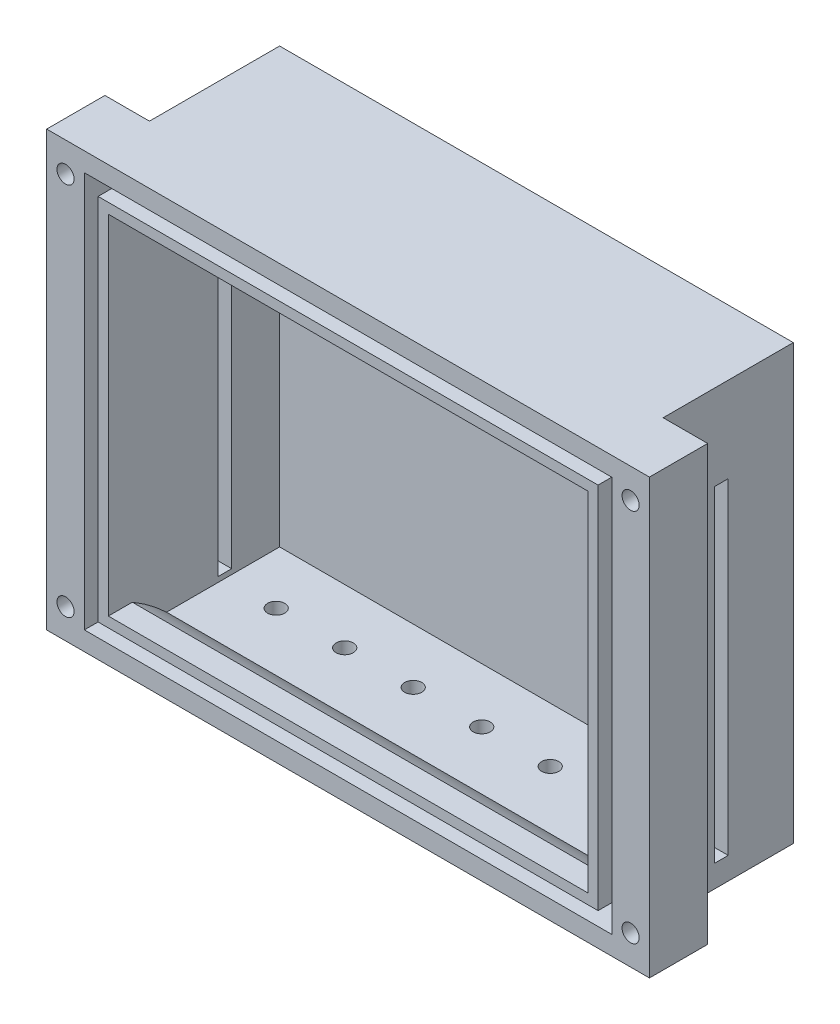
SolidWorks part; units mm, degrees
material "ABS"
ref_plane "Front Plane" through (0, 0, 0) normal (0, 0, 1) x (1, 0, 0)
ref_plane "Top Plane" through (0, 0, 0) normal (0, 1, 0) x (1, 0, 0)
ref_plane "Right Plane" through (0, 0, 0) normal (1, 0, 0) x (0, 0, -1)
sketch "Sketch1" plane through (0, 0, 0) normal (0, 1, 0) x (1, 0, 0)
  circle A0 centre (0, 0) radius 172.5
  dimension "D1" = 345
extrude "Boss-Extrude1" add sketch "Sketch1" along normal blind 10
sketch "Sketch2" plane through (0, 10, 0) normal (0, 1, 0) x (1, 0, 0)
  circle A0 centre (-75.91, -178.72) radius 48.41
  circle A1 centre (75.91, -178.72) radius 48.41
  dimension "D1" = 96.82
  dimension "D2" = 96.82
  dimension "D3" = 151.82
  dimension "D4" = 0
  dimension "D5" = 178.72
  dimension "D6" = 75.91
extrude "Cut-Extrude1" cut sketch "Sketch2" against normal blind 10
sketch "Sketch3" plane through (0, 10, 0) normal (0, 1, 0) x (1, 0, 0)
  line L0 (-75.91, -178.72) -> (75.91, -178.72)
  line L1 (-98.9683, -119.81) -> (98.9683, -119.81)
  line L2 (0, -178.72) -> (0, -205.4095)
  line L3 (0, -116.81) -> (0, -103.1109)
  line L4 (-97.8835, -116.81) -> (97.8835, -116.81)
  arc A0 (97.8835, -116.81) -> (-97.8835, -116.81) centre (0, 0) ccw
  arc A1 (98.9683, -119.81) -> (-98.9683, -119.81) centre (0, 0) ccw
  dimension "D1" = 304.8
  dimension "D2" = 3
  dimension "D4" = 0
extrude "Boss-Extrude2" add sketch "Sketch3" along normal blind 5 contours L1 A1 A0 L4 region at (0, 10, -154.9849)
sketch "Sketch4" plane through (0, 10, 0) normal (0, 1, 0) x (1, 0, 0)
  line L0 (-28.2612, -170.1692) -> (28.2612, -170.1692)
  line L1 (28.2612, -170.1692) -> (28.2612, -183.8361)
  line L2 (28.2612, -183.8361) -> (-30.3005, -183.8361)
  line L3 (-30.3005, -183.8361) -> (-28.2612, -170.1692)
extrude "Cut-Extrude2" cut sketch "Sketch4" against normal blind 497
sketch "Sketch5" plane through (0, 10, 0) normal (0, 1, 0) x (1, 0, 0)
  line L0 (-166.525, 159.566) -> (-166.525, -120.1627)
  line L1 (166.525, 178.4393) -> (166.525, -124.881)
  line L2 (-148.2899, 170.4208) -> (120.6541, 170.4208)
  line L3 (28.2612, -170.1692) -> (-28.2612, -170.1692) construction
  line L5 (-166.525, 170.4208) -> (166.525, 170.4208)
  line L6 (-166.525, 170.4208) -> (-166.525, -186.2191)
  line L7 (-166.525, -186.2191) -> (166.525, -186.2191)
  line L8 (166.525, 170.4208) -> (166.525, -186.2191)
  line L9 (-215.4787, 226.3504) -> (214.5081, 226.3504)
  line L10 (-215.4787, 226.3504) -> (-215.4787, -259.9327)
  line L11 (-215.4787, -259.9327) -> (214.5081, -259.9327)
  line L12 (214.5081, 226.3504) -> (214.5081, -259.9327)
  arc M6 (102.8405, -138.4922) -> (-102.8405, -138.4922) centre (0, 0) ccw
  dimension "D1" = 333.05
  dimension "D2" = 166.525
  dimension "D3" = 340.59
extrude "Cut-Extrude6" cut sketch "Sketch5" against normal blind 497 contours L2 M6 | L1 M6 | L0 M6 region at (-168.9186, 10, 0) region at (0, 10, -171.2529) region at (168.9186, 10, 0)
sketch "Sketch6" plane through (0, 10, 0) normal (0, 1, 0) x (1, 0, 0)
  line L0 (-97.8835, -116.81) -> (97.8835, -116.81)
  line L1 (-97.8835, -116.81) -> (-97.8835, -61.81)
  line L2 (97.8835, -116.81) -> (97.8835, -61.81)
  line L3 (97.8835, -61.81) -> (-97.8835, -61.81)
  line L4 (92.8835, -66.81) -> (-92.8835, -66.81)
  line L5 (-92.8835, -111.81) -> (-92.8835, -66.81)
  line L6 (-92.8835, -111.81) -> (92.8835, -111.81)
  line L7 (92.8835, -111.81) -> (92.8835, -66.81)
  dimension "D1" = 55
  dimension "D2" = 5
extrude "Boss-Extrude3" add sketch "Sketch6" along normal blind 133.35
sketch "Sketch7" plane through (0, 10, 0) normal (0, 1, 0) x (1, 0, 0)
  line L1 (-92.8835, -66.81) -> (92.8835, -66.81)
  line L2 (-92.8835, -66.81) -> (-92.8835, -111.81)
  line L3 (-92.8835, -111.81) -> (92.8835, -111.81)
  line L4 (92.8835, -66.81) -> (92.8835, -111.81)
extrude "Boss-Extrude4" add sketch "Sketch7" along normal blind 5
sketch "Sketch8" plane through (0, 10, 0) normal (0, 1, 0) x (1, 0, 0)
  line L0 (-112.8835, -61.81) -> (-112.8835, -101.2671)
  line L1 (-97.8835, -61.81) -> (97.8835, -61.81)
  line L2 (-97.8835, -61.81) -> (-97.8835, -115.8298)
  line L4 (97.8835, -61.81) -> (97.8835, -115.8298)
  line L6 (112.8835, -46.81) -> (112.8835, -101.2671)
  line L7 (-88.0285, -46.81) -> (112.8835, -46.81)
  line L8 (-112.8835, -46.81) -> (-112.8835, -131.81) construction
  line L9 (-112.8835, -131.81) -> (112.8835, -131.81) construction
  line L10 (112.8835, -46.81) -> (112.8835, -131.81) construction
  line L11 (74.9923, -131.81) -> (76.4976, -131.81)
  line L12 (-97.8835, -116.81) -> (97.8835, -116.81) construction
  line L13 (97.8835, -61.81) -> (97.8835, -116.81) construction
  line L14 (-97.8835, -61.81) -> (-97.8835, -116.81) construction
  line L15 (-112.8835, -46.81) -> (112.8835, -46.81) construction
  line L18 (-112.8835, -61.81) -> (-88.0285, -61.81)
  line L19 (-88.0285, -46.81) -> (-88.0285, -61.81)
  arc A1 (-112.8835, -101.2671) -> (-96.7117, -116.81) centre (0, 0) ccw
  arc A5 (97.8835, -115.8298) -> (112.8835, -101.2671) centre (0, 0) ccw
  line M3 (-97.8835, -116.81) -> (-97.8835, -61.81)
  line M5 (97.8835, -61.81) -> (97.8835, -116.81)
  dimension "D1" = 15
extrude "Boss-Extrude5" add sketch "Sketch8" along normal blind 8 contours L0 A1 L18 M3 | A5 L6 L7 L19 L1 M5 region at (-104.9975, 10, 85.5341) region at (29.9995, 10, 60.2371)
chamfer "Chamfer1" distance 8 angle 38 3 edges at (-97.8835, 18, 88.8199) (4.9275, 18, 61.81) (97.8835, 18, 88.8199) first distance on face at (-97.8835, 51.1, 100.8157) first distance on face at (-50.228, 47.3375, 61.81) first distance on face at (97.8835, 51.1, 100.8157)
fillet "Fillet1" radius 38 3 edges at (-97.8835, 26, 88.8199) (4.9275, 26, 61.81) (97.8835, 26, 88.8199)
sketch "Sketch9" plane through (0, 10, 0) normal (0, 1, 0) x (1, 0, 0)
  circle A0 centre (0, 0) radius 374.0793
extrude "Cut-Extrude7" cut sketch "Sketch9" against normal blind 93
sketch "Sketch10" plane through (0, 10, 0) normal (0, -1, 0) x (1, 0, 0)
  circle A0 centre (0, 0) radius 152.4
  circle A1 centre (0, 0) radius 229.3861
extrude "Cut-Extrude8" cut sketch "Sketch10" against normal blind 93 and the other way blind 93
sketch "Sketch11" plane through (0, 143.35, 0) normal (0, 1, 0) x (1, 0, 0)
  line L0 (47.0835, -61.81) -> (47.0835, -116.81)
  line L1 (97.8835, -61.81) -> (-97.8835, -61.81) construction
  line L2 (-97.8835, -116.81) -> (97.8835, -116.81) construction
  line L3 (97.8835, -116.81) -> (97.8835, -61.81) construction
  line L4 (47.0835, -61.81) -> (-97.8835, -61.81)
  line L5 (-97.8835, -61.81) -> (-97.8835, -116.81)
  line L6 (-97.8835, -116.81) -> (47.0835, -116.81)
  line L8 (-140.8808, -21.3721) -> (150.5625, -21.3721)
  line L9 (-140.8808, -21.3721) -> (-140.8808, -156.1708)
  line L10 (-140.8808, -156.1708) -> (150.5625, -156.1708)
  line L11 (150.5625, -21.3721) -> (150.5625, -156.1708)
  dimension "D1" = 50.8
extrude "Cut-Extrude9" cut sketch "Sketch11" against normal blind 143
sketch "Sketch12" plane through (0, 143.35, 0) normal (0, 1, 0) x (1, 0, 0)
  line L1 (47.0835, -61.81) -> (52.0835, -61.81)
  line L2 (47.0835, -61.81) -> (47.0835, -116.81)
  line L3 (47.0835, -116.81) -> (52.0835, -116.81)
  line L4 (52.0835, -61.81) -> (52.0835, -116.81)
  dimension "D1" = 5
extrude "Boss-Extrude6" add sketch "Sketch12" against normal up to surface (133.35 mm away) up to face at (-25.4, 10, 89.31)
sketch "Sketch14" plane through (0, 143.35, 0) normal (0, 1, 0) x (1, 0, 0)
  line L1 (-92.8835, -66.81) -> (47.0835, -66.81)
  line L2 (-92.8835, -66.81) -> (-92.8835, -111.81)
  line L3 (-92.8835, -111.81) -> (47.0835, -111.81)
  line L4 (47.0835, -66.81) -> (47.0835, -111.81)
extrude "Boss-Extrude7" add sketch "Sketch14" against normal blind 5
sketch "Sketch15" plane through (0, 0, 116.81) normal (0, 0, 1) x (1, 0, 0)
  line L1 (-92.8835, 138.35) -> (47.0835, 138.35)
  line L2 (-92.8835, 138.35) -> (-92.8835, 15)
  line L3 (-92.8835, 15) -> (47.0835, 15)
  line L4 (47.0835, 138.35) -> (47.0835, 15)
extrude "Cut-Extrude11" cut sketch "Sketch15" against normal blind 13
sketch "Sketch16" plane through (0, 0, 116.81) normal (0, 0, 1) x (1, 0, 0)
  line L0 (-107.8835, 143.35) -> (-107.8835, 10)
  line L1 (-92.8835, 138.35) -> (47.0835, 138.35)
  line L2 (-92.8835, 138.35) -> (-92.8835, 15)
  line L3 (-92.8835, 15) -> (47.0835, 15)
  line L4 (47.0835, 138.35) -> (47.0835, 15)
  line L6 (62.0835, 143.35) -> (62.0835, 10)
  line L8 (-107.8835, 143.35) -> (62.0835, 143.35)
  line L9 (-107.8835, 10) -> (62.0835, 10)
  line L10 (-107.8835, 153.35) -> (-107.8835, 0) construction
  line L11 (-107.8835, 0) -> (62.0835, 0) construction
  line L12 (62.0835, 153.35) -> (62.0835, 0) construction
  line L13 (-107.8835, 153.35) -> (62.0835, 153.35) construction
  line L14 (-92.8835, 76.675) -> (47.0835, 76.675)
  line L15 (-92.8835, 127.475) -> (47.0835, 127.475)
  line L16 (-92.8835, 127.475) -> (-92.8835, 25.875)
  line L17 (-92.8835, 25.875) -> (47.0835, 25.875)
  line L18 (47.0835, 127.475) -> (47.0835, 25.875)
  line L19 (-22.9, 127.475) -> (-22.9, 25.875)
  point P22 (-92.8835, 76.675)
  point P25 (-22.9, 138.35)
  line M11 (47.0835, 15) -> (-92.8835, 15)
  line M12 (-92.8835, 15) -> (-92.8835, 138.35)
  line M13 (-92.8835, 138.35) -> (47.0835, 138.35)
  line M14 (47.0835, 138.35) -> (47.0835, 15)
  line M15 (-97.8835, 10) -> (52.0835, 10)
  line M16 (52.0835, 10) -> (52.0835, 143.35)
  line M17 (52.0835, 143.35) -> (-97.8835, 143.35)
  line M18 (-97.8835, 143.35) -> (-97.8835, 10)
  dimension "D2" = 101.6
  dimension "D3" = 0
  dimension "D4" = 0
  dimension "D5" = 0
  dimension "D1" = 15
extrude "Boss-Extrude9" add sketch "Sketch16" against normal blind 17 contours L0 L9 L8 M18 | L4 L2 M18 M15 M16 M17 M14 M11 M12 M13 | L9 L6 L8 M16 | L15 M12 M14 M13 | L17 M12 M11 M14 region at (-102.8835, 76.675, 116.81) region at (-22.9, 141.3432, 116.81) region at (57.0835, 76.675, 116.81) region at (-22.9, 132.9125, 116.81) region at (-22.9, 20.4375, 116.81)
sketch "Sketch17" plane through (0, 0, 116.81) normal (0, 0, 1) x (1, 0, 0)
  line L0 (-95.8835, 130.475) -> (-95.8835, 22.875)
  line L1 (-92.8835, 127.475) -> (47.0835, 127.475)
  line L2 (-92.8835, 127.475) -> (-92.8835, 25.875)
  line L3 (-92.8835, 25.875) -> (47.0835, 25.875)
  line L4 (47.0835, 127.475) -> (47.0835, 25.875)
  line L5 (-95.8835, 22.875) -> (50.0835, 22.875)
  line L6 (50.0835, 130.475) -> (50.0835, 22.875)
  line L7 (-95.8835, 130.475) -> (50.0835, 130.475)
  line L8 (-99.8835, 134.475) -> (54.0835, 134.475)
  line L9 (54.0835, 134.475) -> (54.0835, 18.875)
  line L10 (-99.8835, 18.875) -> (54.0835, 18.875)
  line L11 (-99.8835, 134.475) -> (-99.8835, 18.875)
  dimension "D1" = 3
  dimension "D2" = 4
extrude "Cut-Extrude12" cut sketch "Sketch17" against normal blind 10 contours L8 L11 L10 L9 L0 L7 L6 L5 region at (-22.9, 132.5497, 116.81)
sketch "Sketch20" plane through (0, 0, 116.81) normal (0, 0, 1) x (1, 0, 0)
  line L0 (-107.8835, 143.35) -> (-107.8835, 10) construction
  line L1 (-110.8835, 146.35) -> (65.0835, 146.35)
  line L2 (-110.8835, 146.35) -> (-110.8835, 7)
  line L3 (-110.8835, 7) -> (65.0835, 7)
  line L4 (65.0835, 146.35) -> (65.0835, 7)
  line L5 (62.0835, 143.35) -> (62.0835, 10) construction
  line L6 (-107.8835, 10) -> (62.0835, 10) construction
  line L7 (-107.8835, 143.35) -> (62.0835, 143.35) construction
  line L9 (-107.8835, 143.35) -> (62.0835, 143.35)
  line L10 (-107.8835, 143.35) -> (-107.8835, 10)
  line L11 (-107.8835, 10) -> (62.0835, 10)
  line L12 (62.0835, 143.35) -> (62.0835, 10)
  line L13 (-110.8835, 7) -> (65.0835, 7)
  line L14 (-110.8835, 7) -> (-110.8835, 13.35)
  line L15 (-110.8835, 13.35) -> (65.0835, 13.35)
  line L16 (65.0835, 7) -> (65.0835, 13.35)
  line M13 (-107.8835, 10) -> (62.0835, 10)
  line M14 (62.0835, 10) -> (62.0835, 143.35)
  dimension "D1" = 3
  dimension "D2" = 3
  dimension "D3" = 3
  dimension "D4" = 3
  dimension "D5" = 6.35
chamfer "Chamfer2" distance 10 angle 30 2 edges at (-22.9, 25.875, 99.81) (-22.9, 127.475, 99.81) first distance on face at (-22.9, 25.875, 108.31) first distance on face at (-22.9, 132.9125, 99.81)
extrude "Cut-Extrude17" cut sketch "Sketch20" against normal blind 177.5 contours L15 L2 L3 L4 L10 M14 M13 | L15 L10 M13 M14 region at (-22.9, 8.6165, 116.81) region at (-22.9, 11.675, 116.81)
sketch "Sketch25" plane through (0, 13.35, 0) normal (0, -1, 0) x (-1, 0, 0)
  line L1 (-47.0835, -66.81) -> (92.8835, -66.81)
  line L2 (-47.0835, -66.81) -> (-47.0835, -105.5835)
  line L3 (-47.0835, -105.5835) -> (92.8835, -105.5835)
  line L4 (92.8835, -66.81) -> (92.8835, -105.5835)
extrude "Boss-Extrude11" add sketch "Sketch25" against normal blind 5
sketch "Sketch26" plane through (0, 0, 116.81) normal (0, 0, 1) x (1, 0, 0)
  line L0 (-107.8835, 143.35) -> (-107.8835, 13.35) construction
  line L1 (-110.8835, 143.35) -> (-107.8835, 143.35)
  line L2 (-110.8835, 143.35) -> (-110.8835, 13.35)
  line L3 (-110.8835, 13.35) -> (-107.8835, 13.35)
  line L4 (65.0835, 143.35) -> (65.0835, 13.35)
  line L5 (62.0835, 143.35) -> (62.0835, 13.35) construction
  line L6 (62.0835, 13.35) -> (65.0835, 13.35)
  line L8 (-107.8835, 143.35) -> (-107.8835, 13.35)
  line L10 (62.0835, 143.35) -> (62.0835, 13.35)
  line L11 (62.0835, 143.35) -> (65.0835, 143.35)
  dimension "D1" = 3
  dimension "D2" = 3
extrude "Boss-Extrude12" add sketch "Sketch26" against normal up to surface (17 mm away) up to face at (57.0835, 78.35, 99.81)
sketch "Sketch18" plane through (0, 0, 116.81) normal (0, 0, 1) x (1, 0, 0)
  line L7 (-99.8835, 134.475) -> (-99.8835, 18.875) construction
  line L8 (54.0835, 134.475) -> (54.0835, 18.875) construction
  circle A2 centre (-105.3835, 22) radius 2.5
  circle A3 centre (59.5835, 22) radius 2.5
  circle A4 centre (59.5835, 131.35) radius 2.5
  circle A5 centre (-105.3835, 131.35) radius 2.5
  point P10 (-22.9, 76.675)
  dimension "D4" = 5
  dimension "D5" = 5
  dimension "D10" = 5.5
  dimension "D12" = 5.5
extrude "Cut-Extrude19" cut sketch "Sketch18" against normal blind 26
sketch "Sketch27" plane through (0, 0, 66.81) normal (0, 0, 1) x (1, 0, 0)
  line L0 (47.0835, 138.35) -> (-92.8835, 138.35) construction
  line L1 (-22.9165, 138.35) -> (37.0835, 138.35)
  line L2 (-22.9165, 138.35) -> (-22.9165, 135.35)
  line L3 (-22.9165, 135.35) -> (37.0835, 135.35)
  line L4 (37.0835, 138.35) -> (37.0835, 135.35)
  line L5 (47.0835, 18.35) -> (47.0835, 138.35) construction
  dimension "D1" = 60
  dimension "D2" = 0
  dimension "D3" = 70
  dimension "D4" = 3
extrude "Cut-Extrude20" cut sketch "Sketch27" against normal blind 23
sketch "Sketch28" plane through (0, 18.35, 0) normal (0, 1, 0) x (1, 0, 0)
  line L0 (-92.8835, -99.81) -> (-92.8835, -66.81) construction
  line L1 (-92.8835, -66.81) -> (47.0835, -66.81) construction
  circle A0 centre (-77.8835, -82.81) radius 2.5
  circle A1 centre (-57.8835, -82.81) radius 2.5
  circle A2 centre (-37.8835, -82.81) radius 2.5
  circle A3 centre (-17.8835, -82.81) radius 2.5
  circle A4 centre (2.1165, -82.81) radius 2.5
  circle A5 centre (22.1165, -82.81) radius 2.5
  dimension "D1" = 5
  dimension "D2" = 15
  dimension "D3" = 16
  dimension "D4" = 6
extrude "Cut-Extrude21" cut sketch "Sketch28" against normal blind 10
sketch "Sketch29" plane through (0, 0, 61.81) normal (0, 0, -1) x (-1, 0, 0)
  line L0 (97.8835, 13.35) -> (-52.0835, 13.35) construction
  line L1 (39.6909, 98.35) -> (54.6909, 98.35)
  line L2 (39.6909, 98.35) -> (39.6909, 68.35)
  line L3 (39.6909, 68.35) -> (54.6909, 68.35)
  line L4 (54.6909, 98.35) -> (54.6909, 68.35)
  dimension "D1" = 30
  dimension "D2" = 15
  dimension "D3" = 55
extrude "Boss-Extrude13" add sketch "Sketch29" along normal blind 10
sketch "Sketch30" plane through (-54.6909, 0, 0) normal (-1, 0, 0) x (0, 0, 1)
  line L0 (51.81, 68.35) -> (61.81, 68.35) construction
  line L1 (61.81, 98.35) -> (57.81, 98.35)
  line L2 (61.81, 98.35) -> (61.81, 68.35)
  line L3 (61.81, 68.35) -> (57.81, 68.35)
  line L4 (57.81, 98.35) -> (57.81, 68.35)
  line L5 (57.81, 94.85) -> (61.81, 94.85)
  line L6 (57.81, 71.85) -> (61.81, 71.85)
  point P11 (59.81, 98.35)
  dimension "D1" = 4
  dimension "D2" = 3.5
  dimension "D3" = 3.5
extrude "Cut-Extrude22" cut sketch "Sketch30" against normal blind 21 contours L4 L6 L2 L5 region at (-54.6909, 83.35, 59.81)
chamfer "Chamfer3" distance 6 angle 45 2 edges at (-47.1909, 68.35, 61.81) (-47.1909, 98.35, 61.81)
sketch "Sketch31" plane through (0, 0, 116.81) normal (0, 0, 1) x (1, 0, 0)
  line L0 (-110.8835, 13.35) -> (65.0835, 13.35)
  line L1 (65.0835, 13.35) -> (65.0835, -10.6568)
  line L2 (65.0835, -10.6568) -> (-110.8835, -10.6568)
  line L3 (-110.8835, -10.6568) -> (-110.8835, 13.35)
  line L4 (-92.8835, 76.675) -> (-80.1779, 76.675) construction
  line L5 (-92.8835, 127.475) -> (-92.8835, 25.875) construction
  line L6 (-110.8835, 164.0068) -> (-110.8835, 140)
  line L7 (65.0835, 164.0068) -> (-110.8835, 164.0068)
  line L8 (65.0835, 140) -> (65.0835, 164.0068)
  line L9 (-110.8835, 140) -> (65.0835, 140)
extrude "Cut-Extrude23" cut sketch "Sketch31" against normal blind 71
sketch "Sketch32" plane through (0, 0, 66.81) normal (0, 0, 1) x (1, 0, 0)
  line L0 (-92.8835, 18.35) -> (47.0835, 18.35) construction
  line L1 (-77.2965, 119.346) -> (42.0835, 119.346)
  line L2 (-77.2965, 119.346) -> (-77.2965, 24.35)
  line L3 (-77.2965, 24.35) -> (42.0835, 24.35)
  line L4 (42.0835, 119.346) -> (42.0835, 24.35)
  line L5 (47.0835, 18.35) -> (47.0835, 138.35) construction
  circle A0 centre (-60.0065, 103.09) radius 1.778
  circle A1 centre (-18.1915, 56.608) radius 1.27
  circle A2 centre (5.0835, 30.7) radius 1.778
  circle A3 centre (-18.1915, 114.52) radius 1.27
  circle A4 centre (28.6456, 114.52) radius 1.27
  circle A5 centre (28.6456, 56.608) radius 1.27
  dimension "D5" = 3.556
  dimension "D6" = 72.39
  dimension "D7" = 2.54
  dimension "D8" = 3.556
  dimension "D9" = 6.35
  dimension "D10" = 2.54
  dimension "D11" = 2.54
  dimension "D12" = 2.54
  dimension "D13" = 32.258
  dimension "D14" = 0
  dimension "D15" = 90.17
  dimension "D16" = 0
  dimension "D17" = 0
  dimension "D18" = 65.09
  dimension "D19" = 6.35
  dimension "D20" = 42
  dimension "D1" = 94.996
  dimension "D2" = 119.38
  dimension "D3" = 6
  dimension "D4" = 5
sketch "Sketch33" plane through (-97.8835, 0, 0) normal (-1, 0, 0) x (0, 0, 1)
  line L0 (99.81, 13.35) -> (61.81, 13.35) construction
  line L1 (84.81, 115.1) -> (80.81, 115.1)
  line L2 (84.81, 115.1) -> (84.81, 19.85)
  line L3 (84.81, 19.85) -> (80.81, 19.85)
  line L4 (80.81, 115.1) -> (80.81, 19.85)
  line L6 (66.81, 119.346) -> (66.81, 24.35) construction
  dimension "D1" = 95.25
  dimension "D2" = 6.5
  dimension "D3" = 4
  dimension "D4" = 18
extrude "Cut-Extrude25" cut sketch "Sketch33" against normal blind 182
chamfer "Chamfer5" distance 5 angle 45 2 edges at (-39.6909, 83.35, 51.81) (-54.6909, 83.35, 51.81)
chamfer "Chamfer6" distance 4 angle 45 2 edges at (-47.1909, 98.35, 51.81) (-47.1909, 68.35, 51.81)
fillet "Fillet2" radius 10 2 edges at (-49.6909, 83.35, 51.81) (-44.6909, 83.35, 51.81)
extrude "Cut-Extrude26" cut sketch "Sketch32" against normal blind 10 contours A0 | A2
chamfer "Chamfer7" distance 5 angle 35 3 edges at (-54.6909, 67.1, 61.81) (-39.6909, 67.1, 61.81) (-39.6909, 99.6, 61.81) first distance on face at (-58.2285, 103.09, 61.81)
sketch "Sketch34" plane through (47.0835, 0, 0) normal (-1, 0, 0) x (0, 0, 1)
  line L0 (66.81, 18.35) -> (99.81, 18.35) construction
  line L1 (71.57, 24.7) -> (74.57, 24.7)
  line L2 (71.57, 24.7) -> (71.57, 18.35)
  line L3 (71.57, 18.35) -> (74.57, 18.35)
  line L4 (74.57, 24.7) -> (74.57, 18.35)
  line L5 (66.81, 18.35) -> (66.81, 138.35) construction
  dimension "D1" = 0
  dimension "D2" = 4.76
  dimension "D3" = 3
  dimension "D4" = 6.35
extrude "Boss-Extrude14" add sketch "Sketch34" along normal blind 28.58
fillet "Fillet3" radius 3 1 edges at (18.5035, 24.7, 73.07)
fillet "Fillet4" radius 53 1 edges at (-22.9, 20.1015, 99.81)
fillet "Fillet5" radius 163 1 edges at (-22.9, 137.475, 99.81)
chamfer "Chamfer8" distance 2 angle 55 1 edges at (7.0835, 135.35, 66.81) first distance on face at (-58.2285, 103.09, 66.81)
fillet "Fillet7" radius 10 1 edges at (7.0835, 135.35, 63.9537)
